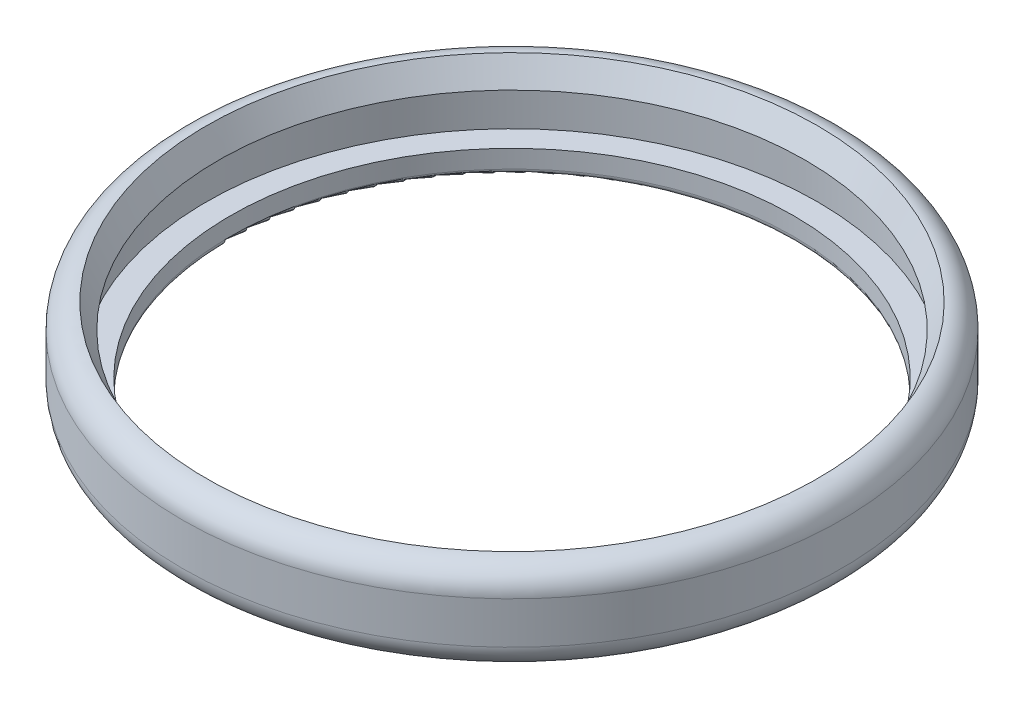
SolidWorks part; units mm, degrees
ref_plane "Front Plane" through (0, 0, 0) normal (0, 0, 1) x (1, 0, 0)
ref_plane "Top Plane" through (0, 0, 0) normal (0, 1, 0) x (1, 0, 0)
ref_plane "Right Plane" through (0, 0, 0) normal (1, 0, 0) x (0, 0, -1)
sketch "Sketch1" plane through (0, 0, 0) normal (0, 0, 1) x (1, 0, 0)
  line L0 (25.5, 0) -> (23.5, 0)
  line L1 (23.5, 0) -> (23.5, -2)
  line L2 (23.5, -2) -> (27.5, -2)
  line L3 (27.5, -2) -> (27.5, 5.5)
  line L4 (27.5, 5.5) -> (25.5, 5.5)
  line L10 (25.5, 0) -> (25.5, 3.5)
  line L13 (0, 0) -> (0, 12.0657) construction
  line L14 (25.5, 5.5) -> (24.5, 3.5)
  line L15 (24.5, 3.5) -> (25.5, 3.5)
  point P0 (0, 0)
  point P1 (25.5, 0)
  dimension "D1" = 25.5
  dimension "D2" = 2
  dimension "D3" = 2
  dimension "D4" = 4
  dimension "D5" = 7.5
  dimension "D6" = 2
  dimension "D7" = 3.5
  dimension "D8" = 1
revolve "Revolve1" add sketch "Sketch1" angle 360 about L13
fillet "Fillet2" radius 2 2 edges at (0, -2, -27.5) (0, 5.5, -27.5)
fillet "Fillet3" radius 0.5 1 edges at (0, -2, -23.5)
